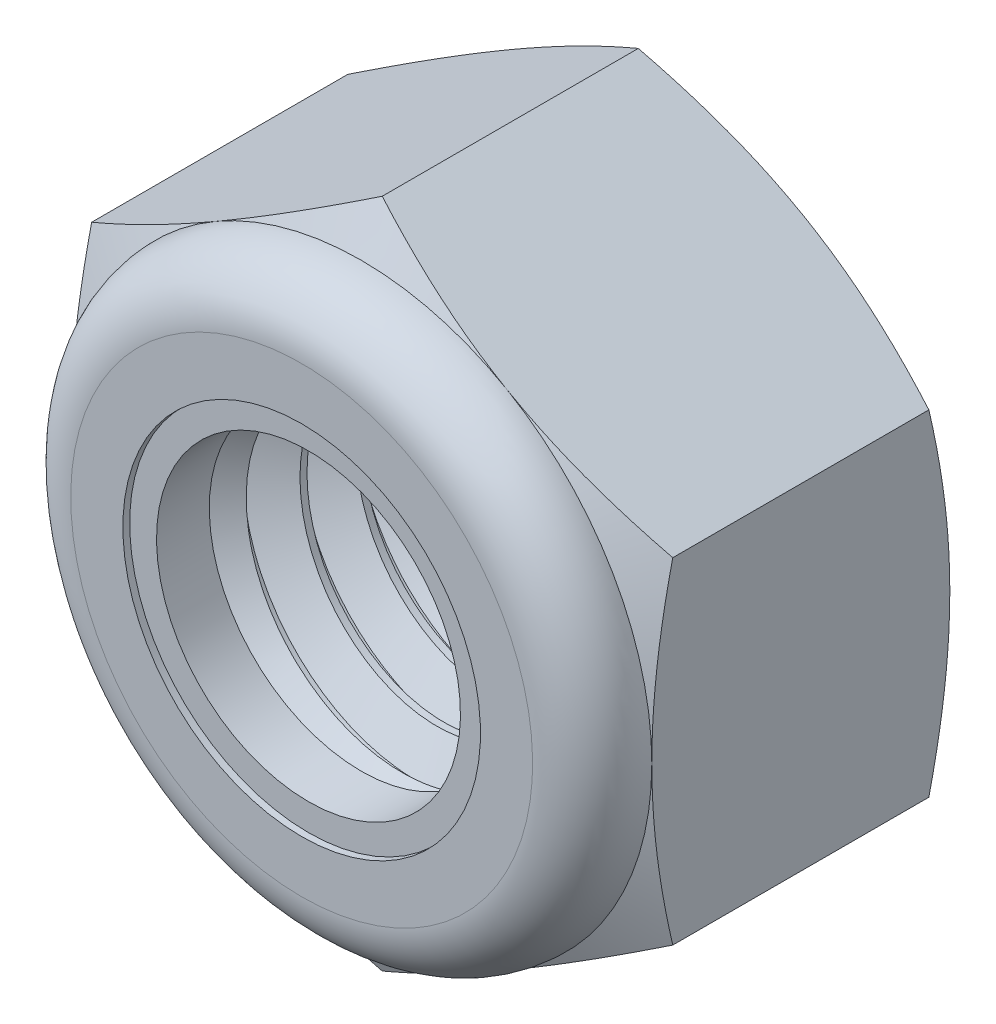
SolidWorks part; units mm, degrees
ref_plane "Front Plane" through (0, 0, 0) normal (0, 0, 1) x (1, 0, 0)
ref_plane "Top Plane" through (0, 0, 0) normal (0, 1, 0) x (1, 0, 0)
ref_plane "Right Plane" through (0, 0, 0) normal (1, 0, 0) x (0, 0, -1)
sketch "Sketch1" plane through (0, 0, 0) normal (1, 0, 0) x (0, 0, -1)
  line L0 (0, 6.5) -> (0, -6.5) construction
  line L1 (-4, 4) -> (4, 4)
  line L2 (-4, 0) -> (4, 0) construction
  line L3 (-4, -6.5) -> (4, -6.5)
  line L4 (-4, -6.5) -> (-4, 6.5)
  line L5 (-4, 6.5) -> (4, 6.5)
  line L6 (4, -6.5) -> (4, 6.5)
  line L7 (-4, -4) -> (4, -4)
  line L8 (3.9219, 4.1353) -> (5.1719, 4.1353) construction
  line L9 (5.1719, 4.1353) -> (4.5469, 3.0528) construction
  line L10 (4.5469, 3.0528) -> (3.9219, 4.1353) construction
  line L11 (4.5469, 3.0528) -> (4.5469, 3.1881) construction
  line L12 (4, 4) -> (5.0937, 4) construction
  line L13 (4.5469, 4) -> (4.5469, 4.1353) construction
  line L15 (5.1328, 4.0677) -> (3.9609, 4.0677) construction
  line L17 (4.4687, 3.1881) -> (4.625, 3.1881) construction
  point P20 (4.5469, 4.0677)
  dimension "Thread Size" = 8
  dimension "Thread Pitch" = 1.25
  dimension "D1" = 0.1562
  dimension "Width" = 13
  dimension "Height" = 8
sketch "Sketch2" plane through (0, 0, 0) normal (1, 0, 0) x (0, 0, -1)
  line L0 (3.6875, 4) -> (4, 4.3125)
  line L1 (-4, 4) -> (4, 4) construction
  line L2 (4, -6.5) -> (4, 6.5) construction
  line L3 (-4, 0) -> (4, 0) construction
  line L4 (-4, 0) -> (4, 0) construction
  line L5 (-4, 5.1667) -> (-4, 4)
  line L6 (-4, -6.5) -> (-4, 6.5) construction
  line L7 (-4, 4) -> (-3.8476, 4)
  line L8 (-2.6667, 6.3476) -> (-2.6667, 4.3125)
  line L9 (-4, 6.5) -> (4, 6.5) construction
  line L10 (-2.6667, 6.5) -> (4, 6.5)
  line L11 (4, 6.5) -> (4, 4.3125)
  line L12 (-3.8476, 5.1667) -> (-3.8476, 4)
  line L13 (-2.3542, 4) -> (3.6875, 4)
  line L14 (4, 4.3125) -> (4, 4) construction
  line L15 (4, 4) -> (3.6875, 4) construction
  line L16 (-2.6667, 4.3125) -> (-2.3542, 4)
  line L17 (-2.6667, 4.3125) -> (4, 4.3125) construction
  line L18 (-3.8476, 4) -> (-3.8476, 3.4) construction
  line L19 (-3.8476, 3.4) -> (-2.6667, 3.4) construction
  line L20 (-2.6667, 3.4) -> (-2.6667, 4.3125) construction
  line L21 (-2.6667, 6.5) -> (4, 20.7967) construction
  arc A0 (-2.6667, 6.5) -> (-4, 5.1667) centre (-2.6667, 5.1667) ccw
  arc A1 (-2.6667, 6.3476) -> (-3.8476, 5.1667) centre (-2.6667, 5.1667) ccw
  dimension "D1" = 1.3333
  dimension "D3" = 0.1524
  dimension "D4" = 0.3125
  dimension "D2" = 6.8
  dimension "D5" = 25
revolve "Revolve1" add sketch "Sketch2" angle 360 about L4
sketch "Sketch3" plane through (0, 0, 0) normal (0, 0, -1) x (-1, 0, 0)
  line L0 (2.4042, 2.4042) -> (-2.4042, -2.4042) construction
  line L1 (6.5, 3.7528) -> (0, 7.5056)
  line L2 (0, 7.5056) -> (-6.5, 3.7528)
  line L3 (-6.5, 3.7528) -> (-6.5, -3.7528)
  line L4 (-6.5, -3.7528) -> (0, -7.5056)
  line L5 (0, -7.5056) -> (6.5, -3.7528)
  line L6 (6.5, -3.7528) -> (6.5, 3.7528)
  line L8 (-2.4042, 2.4042) -> (2.4042, -2.4042) construction
  circle A0 centre (0, 0) radius 6.5 construction
  circle A1 centre (0, 0) radius 6.3476
  circle A2 centre (0, 0) radius 3.4 construction
extrude "Boss-Extrude1" add sketch "Sketch3" along normal up to surface (4 mm away) from vertex up to face at (0, -6.5, -4) starting at point (0, 6.3476, 2.6667)
sketch "Sketch4" plane through (0, 0, 0) normal (1, 0, 0) x (0, 0, -1)
  line L0 (-2.6667, 6.5) -> (-0.8155, 10.4699)
  line L1 (-2.6667, 6.5) -> (4, 20.7967) construction
  line L2 (-0.8155, 10.4699) -> (2.1488, 10.4699)
  line L4 (2.1488, 10.4699) -> (4, 6.5)
  line L5 (0.6667, 7.5056) -> (0.6667, 10.4699) construction
  line L6 (4, 7.5056) -> (-2.6667, 7.5056) construction
  line L7 (-2.6667, 6.5) -> (-2.6667, 11.7199)
  line L8 (-2.6667, 11.7199) -> (4, 11.7199)
  line L9 (4, 11.7199) -> (4, 6.5)
  line L10 (0.6667, 10.4699) -> (0.6667, 11.7199) construction
  line L11 (3.9219, 4.1353) -> (5.1719, 4.1353) construction
revolve "Cut-Revolve1" cut sketch "Sketch4" angle 360 about L2
sketch "Sketch5" plane through (0, 0, 0) normal (1, 0, 0) x (0, 0, -1)
  line L0 (-3.8476, 4) -> (-3.8476, 3.4) construction
  line L1 (-3.8476, 3.4) -> (-2.6667, 3.4) construction
  line L2 (-2.6667, 3.4) -> (-2.6667, 4.3125) construction
  line L3 (-3.8476, 5.1667) -> (-3.8476, 3.4)
  line L4 (-3.8476, 3.4) -> (-2.6667, 3.4)
  line L5 (-2.6667, 3.4) -> (-2.6667, 6.3476)
  arc A0 (-2.6667, 6.3476) -> (-3.8476, 5.1667) centre (-2.6667, 5.1667) ccw construction
  arc A1 (-2.6667, 6.3476) -> (-3.8476, 5.1667) centre (-2.6667, 5.1667) ccw
revolve "Revolve2" add sketch "Sketch5" angle 360 about L4
sketch "Sketch6" plane through (0, 0, -4) normal (0, 0, -1) x (-1, 0, 0)
  circle A0 centre (0, 0) radius 4
ref_axis "Center Axis 1" through (0, 0, 4) along (0, 0, -1)
curve "Helix/Spiral1" pitch 1.25 height 8 radius 4 centre (0, 0, -4) axis (0, 0, 1) start towards (0, 1, 0)
sketch "Sketch7" plane through (0, 0, 0) normal (1, 0, 0) x (0, 0, -1)
  line L0 (5.1328, 4.0677) -> (3.9609, 4.0677) construction
  line L1 (4.4687, 3.1881) -> (4.625, 3.1881) construction
  line L2 (5.1719, 4.1353) -> (4.5469, 3.0528) construction
  line L3 (4.5469, 3.0528) -> (3.9219, 4.1353) construction
  line L4 (5.1328, 4.0677) -> (3.9609, 4.0677)
  line L5 (4.4687, 3.1881) -> (4.625, 3.1881)
  line L6 (5.1328, 4.0677) -> (4.625, 3.1881)
  line L7 (4.4687, 3.1881) -> (3.9609, 4.0677)
sweep "Sweep1" add profiles "Sketch7" path "Helix/Spiral1"
sketch "Sketch8" plane through (0, 0, 0) normal (1, 0, 0) x (0, 0, -1)
  line L0 (-4, 4) -> (-4, 6.5)
  line L1 (-3.8476, 5.1667) -> (-3.8476, 4) construction
  line L2 (-4, 6.5) -> (-12, 6.5)
  line L3 (-3.8476, 5.1667) -> (-3.8476, 4)
  line L4 (-2.6667, 4.3125) -> (-2.3542, 4) construction
  line L5 (-2.6667, 4.3125) -> (-1.407, 3.0528)
  line L6 (4.5469, 3.0528) -> (-12, 3.0528) construction
  line L7 (-2.6667, 4.3125) -> (-2.6667, 6.3476)
  line L8 (-4, 6.5) -> (4, 6.5) construction
  line L10 (-3.8476, 4) -> (-4, 4)
  line L12 (-12, 0) -> (-1.407, 0)
  line L13 (-4, 0) -> (4, 0) construction
  line L14 (-1.407, 0) -> (-1.407, 3.0528)
  line L15 (3.6875, 4) -> (4, 4.3125) construction
  line L16 (2.7403, 3.0528) -> (4, 4.3125)
  line L17 (2.7403, 3.0528) -> (2.7403, 0)
  line L18 (2.7403, 0) -> (5.7969, 0)
  line L19 (5.7969, 0) -> (5.7969, 4.3125)
  line L20 (5.7969, 4.3125) -> (4, 4.3125)
  line L21 (-12, 0) -> (-12, 6.5)
  line L23 (4.5469, 3.0528) -> (5.7969, 3.0528) construction
  line L24 (3.9219, 4.1353) -> (5.1719, 4.1353) construction
  arc A0 (-2.6667, 6.3476) -> (-3.8476, 5.1667) centre (-2.6667, 5.1667) ccw construction
  arc A1 (-2.6667, 6.3476) -> (-3.8476, 5.1667) centre (-2.6667, 5.1667) ccw
revolve "Cut-Revolve2" cut sketch "Sketch8" angle 360 about L2
equation "\"D1@Sketch1\"=\"Thread Pitch@Sketch1\"/8"
equation "\"D1@Sketch2\"=\"Height@Sketch1\"/6"
equation "\"D4@Sketch2\"=.25*\"Thread Pitch@Sketch1\""
equation "\"D2@Sketch2\"=.85*\"Thread Size@Sketch1\""
equation "\"D4@Helix/Spiral1\"=\"Thread Pitch@Sketch1\""
equation "\"D3@Helix/Spiral1\"=\"Height@Sketch1\""
